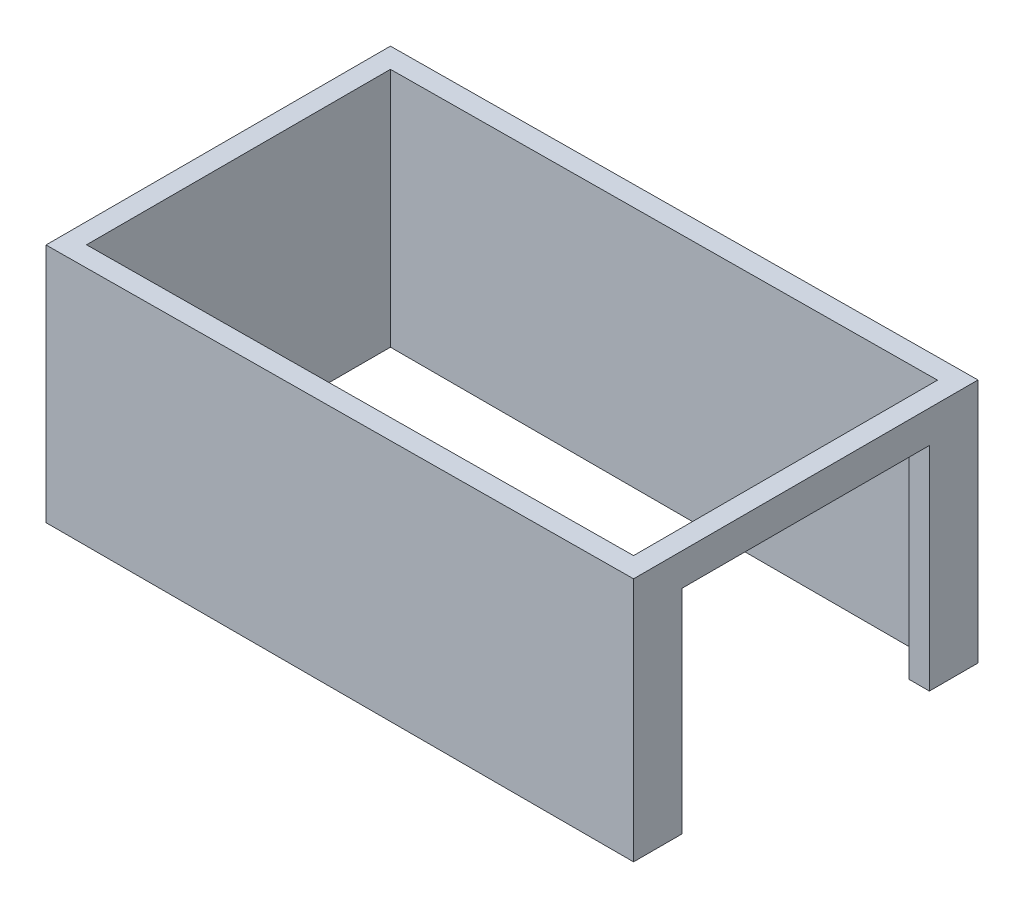
SolidWorks part; units mm, degrees
ref_plane "Спереди" through (0, 0, 0) normal (0, 0, 1) x (1, 0, 0)
ref_plane "Сверху" through (0, 0, 0) normal (0, 1, 0) x (1, 0, 0)
ref_plane "Справа" through (0, 0, 0) normal (1, 0, 0) x (0, 0, -1)
sketch "Эскиз1" plane through (0, 0, 0) normal (0, 1, 0) x (1, 0, 0)
  line L1 (0, 0) -> (5400, 0)
  line L2 (0, 0) -> (0, 3000)
  line L3 (0, 3000) -> (5400, 3000)
  line L4 (5400, 0) -> (5400, 3000)
extrude "Вытянуть-Тонкостенный1" add sketch "Эскиз1" along normal blind 2420 thin thin type one direction wall 200
sketch "Эскиз2" plane through (5600, 0, 0) normal (1, 0, 0) x (0, 0, -1)
  line L0 (-200, 0) -> (3200, 0) construction
  line L1 (280, 0) -> (2720, 0)
  line L2 (280, 0) -> (280, 2100)
  line L3 (280, 2100) -> (2720, 2100)
  line L4 (2720, 0) -> (2720, 2100)
extrude "Вырез-Вытянуть1" cut sketch "Эскиз2" against normal up to next
sketch "Эскиз3" plane through (0, 0, -3200) normal (0, 0, -1) x (-1, 0, 0)
  line L0 (-5600, 2420) -> (200, 2420)
  line L1 (200, 2420) -> (200, 2374)
  line L2 (200, 2420) -> (200, 0) construction
  line L3 (200, 2374) -> (-5600, 2420)
extrude "Вырез-Вытянуть2" cut sketch "Эскиз3" against normal through all
